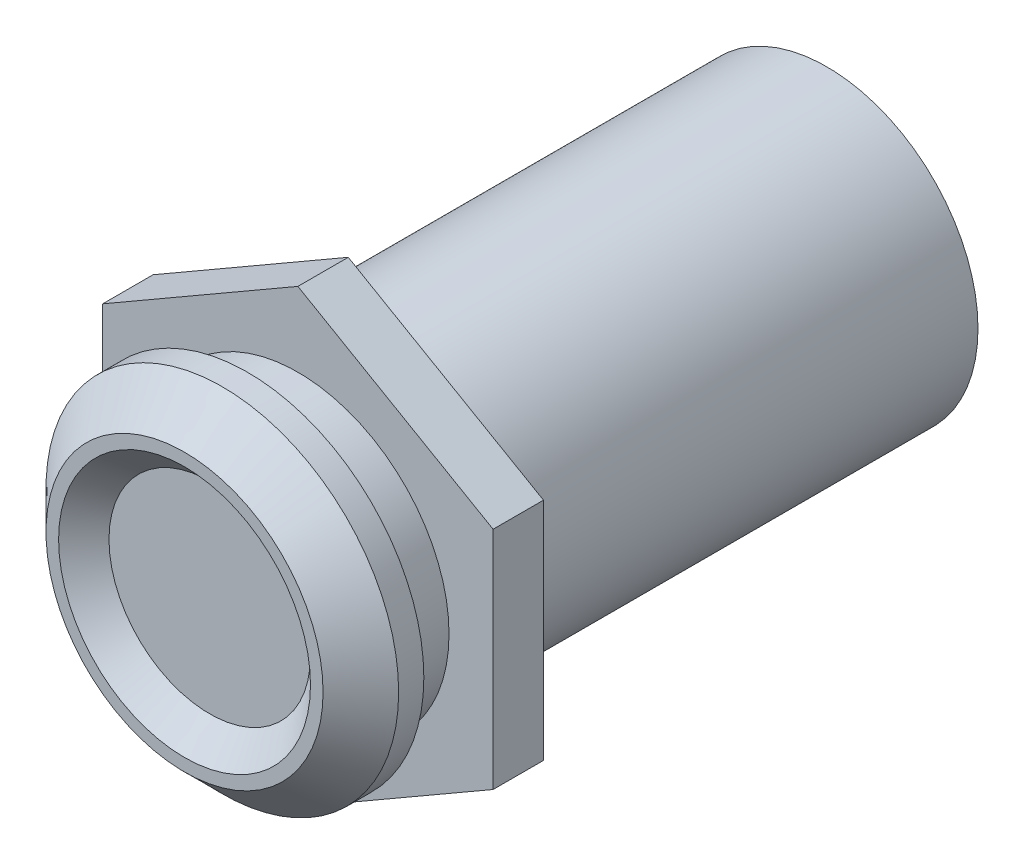
SolidWorks part; units mm, degrees
ref_plane "Front" through (0, 0, 0) normal (0, 0, 1) x (1, 0, 0)
ref_plane "Top" through (0, 0, 0) normal (0, 1, 0) x (1, 0, 0)
ref_plane "Right" through (0, 0, 0) normal (1, 0, 0) x (0, 0, -1)
sketch "Sketch1" plane through (0, 0, 0) normal (0, 0, 1) x (1, 0, 0)
  circle A0 centre (0, 0) radius 7
  dimension "D1" = 14
extrude "Boss-Extrude1" add sketch "Sketch1" along normal blind 1
sketch "Sketch2" plane through (0, 0, 1) normal (0, 0, 1) x (1, 0, 0)
  circle A1 centre (0, 0) radius 7
  circle A2 centre (0, 0) radius 7
  dimension "D1" = 0
extrude "Boss-Extrude2" add sketch "Sketch2" along normal blind 1.5 draft 45
sketch "Sketch3" plane through (0, 0, 2.5) normal (0, 0, 1) x (1, 0, 0)
  circle A2 centre (0, 0) radius 5
  circle A3 centre (0, 0) radius 5
  dimension "D1" = 0.5
extrude "Cut-Extrude1" cut sketch "Sketch3" against normal blind 1 draft 45
sketch "Sketch4" plane through (0, 0, 0) normal (0, 0, 1) x (1, 0, 0)
  circle A0 centre (0, 0) radius 6
  dimension "D1" = 12
extrude "Boss-Extrude3" add sketch "Sketch4" against normal blind 23
ref_plane "Plane1" through (0, 0, -2) normal (0, 0, 1) x (1, 0, 0)
sketch "Sketch5" plane through (0, 0, -2) normal (0, 0, 1) x (1, 0, 0)
  line L1 (0, 8.9489) -> (-7.75, 4.4745)
  line L2 (-7.75, 4.4745) -> (-7.75, -4.4745)
  line L3 (-7.75, -4.4745) -> (0, -8.9489)
  line L4 (0, -8.9489) -> (7.75, -4.4745)
  line L5 (7.75, -4.4745) -> (7.75, 4.4745)
  line L6 (7.75, 4.4745) -> (0, 8.9489)
  circle A0 centre (0, 0) radius 7.75 construction
  dimension "D1" = 15.5
extrude "Nut" add sketch "Sketch5" against normal blind 2
sketch "Panel Cut Guide" plane through (0, 0, 0) normal (0, 0, 1) x (1, 0, 0)
  circle A0 centre (0, 0) radius 6.05
  dimension "D1" = 12.1
